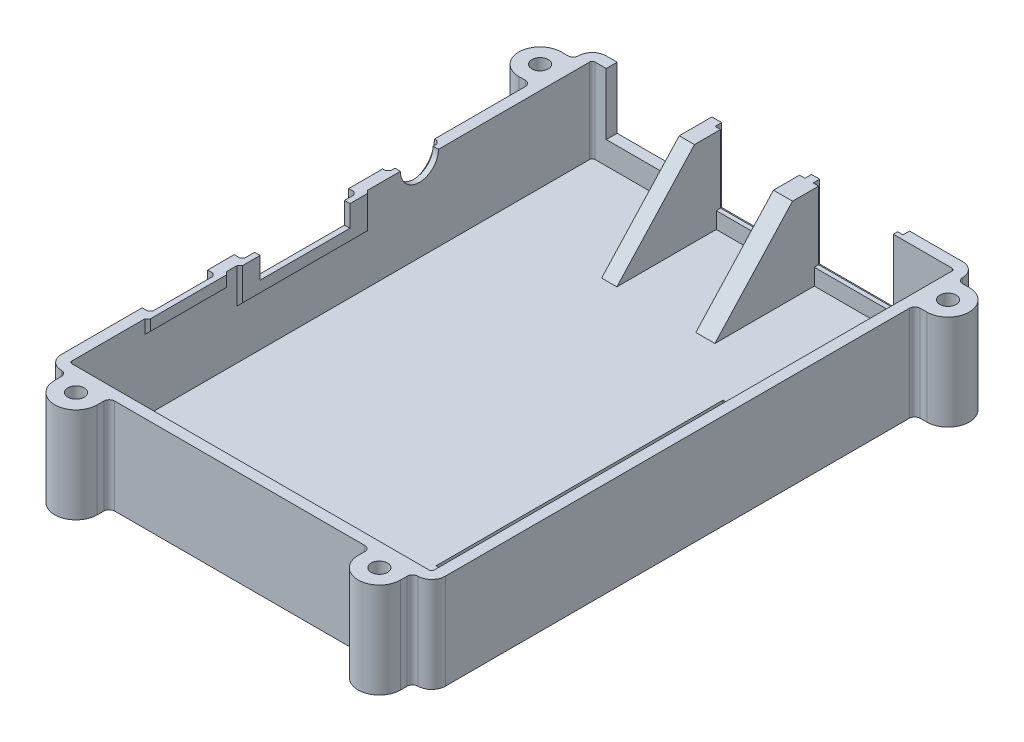
SolidWorks part; units mm, degrees
ref_plane "Front Plane" through (0, 0, 0) normal (0, 0, 1) x (1, 0, 0)
ref_plane "Top Plane" through (0, 0, 0) normal (0, 1, 0) x (1, 0, 0)
ref_plane "Right Plane" through (0, 0, 0) normal (1, 0, 0) x (0, 0, -1)
sketch "Sketch2" plane through (0, 0, 0) normal (0, 1, 0) x (1, 0, 0)
  line L1 (2.5, 0) -> (68, 0)
  line L2 (0, 2.5) -> (0, 97.5)
  line L3 (2.5, 100) -> (68, 100)
  line L4 (70.5, 2.5) -> (70.5, 97.5)
  arc A0 (0, 2.5) -> (2.5, 0) centre (2.5, 2.5) ccw
  arc A1 (68, 0) -> (70.5, 2.5) centre (68, 2.5) ccw
  arc A2 (70.5, 97.5) -> (68, 100) centre (68, 97.5) ccw
  arc A3 (2.5, 100) -> (0, 97.5) centre (2.5, 97.5) ccw
  point P7 (0, 0)
  point P10 (70.5, 0)
  point P13 (70.5, 100)
  point P16 (0, 100)
  dimension "D3" = 2.5
  dimension "D1" = 70.5
  dimension "D2" = 100
extrude "Base" add sketch "Sketch2" along normal blind 17.5
shell "Shell" thickness 2 removed face at (35.25, 17.5, -50)
sketch "Sketch14" plane through (0, 0, 0) normal (0, -1, 0) x (1, 0, 0)
  line L0 (35.25, 0) -> (35.25, -100) construction
  line L2 (68, -100) -> (2.5, -100) construction
  line L3 (-2.2, -88.7) -> (0, -88.7)
  line L4 (0, -97.5) -> (0, -2.5) construction
  line L5 (0, -88.7) -> (0, -96.5)
  line L6 (0, -96.5) -> (-2.2, -96.5)
  line L7 (3.5, 2.2) -> (3.5, 0)
  line L8 (2.5, 0) -> (68, 0) construction
  line L9 (3.5, 0) -> (11.3, 0)
  line L10 (11.3, 0) -> (11.3, 2.2)
  line L11 (72.7, -88.7) -> (70.5, -88.7)
  line L12 (70.5, -96.5) -> (72.7, -96.5)
  line L13 (70.5, -88.7) -> (70.5, -96.5)
  line L14 (59.2, 0) -> (59.2, 2.2)
  line L15 (67, 0) -> (59.2, 0)
  line L16 (67, 2.2) -> (67, 0)
  line L17 (2.5, 0) -> (68, 0) construction
  arc A0 (-2.2, -88.7) -> (-2.2, -96.5) centre (-2.2, -92.6) ccw
  arc A1 (3.5, 2.2) -> (11.3, 2.2) centre (7.4, 2.2) cw
  arc A2 (72.7, -88.7) -> (72.7, -96.5) centre (72.7, -92.6) cw
  arc A3 (67, 2.2) -> (59.2, 2.2) centre (63.1, 2.2) ccw
  dimension "D1" = 2.2
  dimension "D2" = 7.8
  dimension "D3" = 3.5
  dimension "D4" = 3.5
extrude "Clamps" add sketch "Sketch14" against normal up to surface (17.5 mm away) up to face at (35.25, 17.5, -50)
fillet "Clamp Fillets" radius 1 8 edges at (59.2, 8.75, 0) (67, 8.75, 0) (11.3, 8.75, 0) (3.5, 8.75, 0) (0, 8.75, -96.5) (0, 8.75, -88.7) (70.5, 8.75, -88.7) (70.5, 8.75, -96.5)
sketch "Sketch20" plane through (0, 0, 0) normal (0, -1, 0) x (1, 0, 0)
  circle A0 centre (7.4, 2.2) radius 1.5
  circle A1 centre (63.1, 2.2) radius 1.5
  circle A2 centre (72.7, -92.6) radius 1.5
  circle A3 centre (-2.2, -92.6) radius 1.5
  arc A4 (11.3, 2.2) -> (3.5, 2.2) centre (7.4, 2.2) ccw construction
  arc A5 (67, 2.2) -> (59.2, 2.2) centre (63.1, 2.2) ccw construction
  arc A6 (-2.2, -88.7) -> (-2.2, -96.5) centre (-2.2, -92.6) ccw construction
  arc A7 (72.7, -96.5) -> (72.7, -88.7) centre (72.7, -92.6) ccw construction
  dimension "D1" = 3
extrude "Clamp Holes" cut sketch "Sketch20" against normal through all
sketch "Sketch21" plane through (0, 0, 0) normal (0, -1, 0) x (1, 0, 0)
  circle A0 centre (7.4, 2.2) radius 2.5
  circle A1 centre (63.1, 2.2) radius 2.5
  circle A2 centre (72.7, -92.6) radius 2.5
  circle A3 centre (-2.2, -92.6) radius 2.5
  circle A4 centre (-2.2, -92.6) radius 1.5 construction
  circle A5 centre (7.4, 2.2) radius 1.5 construction
  circle A6 centre (63.1, 2.2) radius 1.5 construction
  circle A7 centre (72.7, -92.6) radius 1.5 construction
  dimension "D1" = 5
extrude "Clamp Countersinks" cut sketch "Sketch21" against normal blind 3
chamfer "Clamp Countersink Chamfers" distance 0.3 angle 45 4 edges at (-2.2, 0, -95.1) (72.7, 0, -95.1) (63.1, 0, -0.3) (7.4, 0, -0.3)
sketch "Sketch24" plane through (0, 0, -100) normal (0, 0, -1) x (-1, 0, 0)
  line L0 (-68, 17.5) -> (-2.5, 17.5) construction
  line L1 (-57.25, 17.5) -> (-42.75, 17.5)
  line L2 (-57.25, 17.5) -> (-57.25, 5)
  line L3 (-57.25, 5) -> (-42.75, 5)
  line L4 (-42.75, 17.5) -> (-42.75, 5)
  line L6 (0, 17.5) -> (0, 0) construction
  line L7 (-39.25, 17.5) -> (-24.75, 17.5)
  line L8 (-39.25, 17.5) -> (-39.25, 5)
  line L9 (-39.25, 5) -> (-24.75, 5)
  line L10 (-24.75, 17.5) -> (-24.75, 5)
  dimension "D1" = 14.5
  dimension "D2" = 24.75
  dimension "D3" = 42.75
  dimension "D4" = 12.5
extrude "USB Cutout" cut sketch "Sketch24" against normal blind 18.25
sketch "Sketch25" plane through (0, 0, -100) normal (0, 0, -1) x (-1, 0, 0)
  line L0 (-42.75, 17.5) -> (-39.25, 17.5) construction
  line L1 (-41.75, 17.5) -> (-58.25, 17.5)
  line L2 (-41.75, 17.5) -> (-41.75, 4)
  line L3 (-41.75, 4) -> (-58.25, 4)
  line L4 (-58.25, 17.5) -> (-58.25, 4)
  line L6 (-24.75, 17.5) -> (-2.5, 17.5) construction
  line L7 (-23.75, 17.5) -> (-40.25, 17.5)
  line L8 (-23.75, 17.5) -> (-23.75, 4)
  line L9 (-23.75, 4) -> (-40.25, 4)
  line L10 (-40.25, 17.5) -> (-40.25, 4)
  line L12 (-57.25, 17.5) -> (-57.25, 5) construction
  line L13 (-42.75, 5) -> (-42.75, 17.5) construction
  line L14 (-39.25, 17.5) -> (-39.25, 5) construction
  line L15 (-24.75, 5) -> (-24.75, 17.5) construction
  point P18 (-57.25, 11.25)
  dimension "D1" = 1
  dimension "D2" = 1
  dimension "D3" = 1
  dimension "D4" = 1
  dimension "D5" = 13.5
extrude "USB Approach" cut sketch "Sketch25" against normal blind 1.2
sketch "Sketch26" plane through (42.75, 0, 0) normal (1, 0, 0) x (0, 0, -1)
  line L0 (98, 2) -> (98, 17.5)
  line L1 (98, 17.5) -> (94, 17.5)
  line L2 (98, 2) -> (79.75, 2)
  line L3 (79.75, 2) -> (94, 17.5)
  line L4 (100, 4) -> (100, 17.5) construction
  line L5 (98.8, 5) -> (98.8, 17.5) construction
  dimension "D1" = 6
  dimension "D2" = 19.05
extrude "USB Inner Support" add sketch "Sketch26" against normal up to surface (3.5 mm away) up to face at (39.25, 11.25, -98.4)
sketch "Sketch27" plane through (24.75, 0, 0) normal (1, 0, 0) x (0, 0, -1)
  line L0 (98, 2) -> (98, 17.5)
  line L1 (98, 17.5) -> (94, 17.5)
  line L2 (98, 2) -> (79.75, 2)
  line L3 (79.75, 2) -> (94, 17.5)
  line L4 (100, 4) -> (100, 17.5) construction
  line L5 (98.8, 5) -> (98.8, 17.5) construction
  dimension "D1" = 6
  dimension "D2" = 19.05
extrude "USB Outer Support" add sketch "Sketch27" against normal blind 2.8
sketch "Sketch28" plane through (0, 0, -100) normal (0, 0, -1) x (-1, 0, 0)
  line L0 (-23.75, 17.5) -> (-2.5, 17.5) construction
  line L1 (-21.95, 17.5) -> (-4.55, 17.5)
  line L2 (-21.95, 17.5) -> (-21.95, 6.2)
  line L3 (-21.95, 6.2) -> (-4.55, 6.2)
  line L4 (-4.55, 17.5) -> (-4.55, 6.2)
  line L5 (0, 17.5) -> (0, 0) construction
  dimension "D1" = 17.4
  dimension "D2" = 4.55
  dimension "D3" = 11.3
extrude "RJ45 Cutout" cut sketch "Sketch28" against normal blind 22.7
sketch "Sketch29" plane through (2, 0, 0) normal (1, 0, 0) x (0, 0, -1)
  line L0 (97.5, 17.5) -> (2.5, 17.5) construction
  line L1 (15.85, 17.5) -> (30.85, 17.5)
  line L2 (15.85, 17.5) -> (15.85, 15)
  line L3 (15.85, 15) -> (30.85, 15)
  line L4 (30.85, 17.5) -> (30.85, 15)
  line L5 (0, 17.5) -> (0, 0) construction
  line L6 (32.75, 17.5) -> (56.75, 17.5)
  line L7 (32.75, 17.5) -> (32.75, 11.07)
  line L8 (32.75, 11.07) -> (56.75, 11.07)
  line L9 (56.75, 17.5) -> (56.75, 11.07)
  dimension "D1" = 24
  dimension "D2" = 15
  dimension "D3" = 15.85
  dimension "D4" = 32.75
  dimension "D5" = 2.5
  dimension "D6" = 6.43
extrude "HDMI Support" add sketch "Sketch29" along normal blind 0.5
chamfer "HDMI Support Chamfer" distance 0.5 angle 45 6 edges at (2.5, 14.285, -56.75) (2.5, 11.07, -44.75) (2.5, 14.285, -32.75) (2.5, 16.25, -30.85) (2.5, 15, -23.35) (2.5, 16.25, -15.85)
sketch "Sketch30" plane through (0, 0, 0) normal (-1, 0, 0) x (0, 0, 1)
  line L0 (-87.7, 17.5) -> (-2.5, 17.5) construction
  line L1 (-34.25, 17.5) -> (-55.25, 17.5)
  line L2 (-34.25, 17.5) -> (-34.25, 11.57)
  line L3 (-34.25, 11.57) -> (-55.25, 11.57)
  line L4 (-55.25, 17.5) -> (-55.25, 11.57)
  line L5 (0, 17.5) -> (0, 0) construction
  line L6 (-29.35, 17.5) -> (-17.35, 17.5)
  line L7 (-29.35, 17.5) -> (-29.35, 15.5)
  line L8 (-29.35, 15.5) -> (-17.35, 15.5)
  line L9 (-17.35, 17.5) -> (-17.35, 15.5)
  dimension "D1" = 12
  dimension "D2" = 21
  dimension "D3" = 17.35
  dimension "D4" = 34.25
  dimension "D5" = 5.93
  dimension "D6" = 2
extrude "HDMI Approach" cut sketch "Sketch30" against normal blind 1.5
sketch "Sketch31" plane through (1.5, 0, 0) normal (-1, 0, 0) x (0, 0, 1)
  line L0 (-34.25, 17.5) -> (-55.25, 17.5) construction
  line L1 (-53, 17.5) -> (-36.5, 17.5)
  line L2 (-53, 17.5) -> (-53, 13.57)
  line L3 (-53, 13.57) -> (-36.5, 13.57)
  line L4 (-36.5, 17.5) -> (-36.5, 13.57)
  line L5 (-55.25, 17.5) -> (-55.25, 11.57) construction
  line L6 (-34.25, 11.57) -> (-34.25, 17.5) construction
  line L7 (-55.25, 11.57) -> (-34.25, 11.57) construction
  dimension "D1" = 2.25
  dimension "D2" = 2.25
  dimension "D3" = 2
extrude "HDMI Cutout" cut sketch "Sketch31" against normal blind 1
chamfer "HDMI Approach Chamfer" distance 0.5 angle 45 6 edges at (1.5, 16.5, -17.35) (1.5, 15.5, -23.35) (1.5, 16.5, -29.35) (1.5, 14.535, -34.25) (1.5, 11.57, -44.75) (1.5, 14.535, -55.25)
sketch "Sketch32" plane through (0, 0, 0) normal (-1, 0, 0) x (0, 0, 1)
  line L0 (-87.7, 17.5) -> (-55.25, 17.5) construction
  line L1 (0, 17.5) -> (0, 0) construction
  circle A0 centre (-66.25, 17.5) radius 3.5
  dimension "D1" = 7
  dimension "D2" = 66.25
extrude "Audio Cutout" cut sketch "Sketch32" against normal blind 2
sketch "Sketch33" plane through (0, 0, 0) normal (-1, 0, 0) x (0, 0, 1)
  circle A0 centre (-66.25, 17.5) radius 4.75
  arc A1 (-69.75, 17.5) -> (-62.75, 17.5) centre (-66.25, 17.5) ccw construction
  dimension "D1" = 9.5
extrude "Audio Approach" cut sketch "Sketch33" against normal blind 1
chamfer "Audio Approach Chamfer" distance 0.5 angle 45 1 edges at (1, 12.75, -66.25)
sketch "Sketch34" plane through (0, 0, 0) normal (0, -1, 0) x (1, 0, 0)
  line L0 (70.5, -2.5) -> (70.5, -87.7) construction
  line L1 (52.5, -18.8) -> (58.5, -18.8)
  line L2 (52.5, -18.8) -> (52.5, -71.5)
  line L3 (52.5, -71.5) -> (58.5, -71.5)
  line L4 (58.5, -18.8) -> (58.5, -71.5)
  line L5 (12.3, 0) -> (58.2, 0) construction
  point P6 (55.5, -18.8)
  dimension "D1" = 6
  dimension "D2" = 52.7
  dimension "D3" = 12
  dimension "D4" = 18.8
extrude "Header Cutout" cut sketch "Sketch34" against normal blind 2
sketch "Sketch35" plane through (0, 0, 0) normal (0, -1, 0) x (1, 0, 0)
  line L0 (55.5, -18.8) -> (55.5, -71.5) construction
  line L1 (58.5, -18.8) -> (52.5, -18.8) construction
  line L2 (52.5, -71.5) -> (58.5, -71.5) construction
  line L3 (52.5, -45.15) -> (58.5, -45.15) construction
  line L4 (52.5, -18.8) -> (52.5, -71.5) construction
  line L5 (58.5, -71.5) -> (58.5, -18.8) construction
  line L6 (56, -18.8) -> (55, -18.8)
  line L7 (55, -18.8) -> (55, -19.8)
  line L8 (55, -19.8) -> (53.5, -19.8)
  line L9 (53.5, -19.8) -> (53.5, -24.7625)
  line L10 (53.5, -24.7625) -> (52.5, -24.7625)
  line L11 (52.5, -24.7625) -> (52.5, -25.7625)
  line L12 (52.5, -25.7625) -> (53.5, -25.7625)
  line L13 (53.5, -25.7625) -> (53.5, -37.6875)
  line L14 (53.5, -37.6875) -> (52.5, -37.6875)
  line L15 (52.5, -37.6875) -> (52.5, -38.6875)
  line L16 (52.5, -38.6875) -> (53.5, -38.6875)
  line L17 (53.5, -38.6875) -> (53.5, -43.65)
  line L18 (53.5, -43.65) -> (55, -43.65)
  line L19 (55, -43.65) -> (55, -44.65)
  line L20 (55, -44.65) -> (52.5, -44.65)
  line L21 (52.5, -44.65) -> (52.5, -45.65)
  line L22 (56, -71.5) -> (55, -71.5)
  line L23 (55, -45.65) -> (52.5, -45.65)
  line L24 (55, -46.65) -> (55, -45.65)
  line L25 (53.5, -46.65) -> (55, -46.65)
  line L26 (53.5, -51.6125) -> (53.5, -46.65)
  line L27 (52.5, -51.6125) -> (53.5, -51.6125)
  line L28 (52.5, -52.6125) -> (52.5, -51.6125)
  line L29 (53.5, -52.6125) -> (52.5, -52.6125)
  line L30 (53.5, -64.5375) -> (53.5, -52.6125)
  line L31 (52.5, -64.5375) -> (53.5, -64.5375)
  line L32 (52.5, -65.5375) -> (52.5, -64.5375)
  line L33 (53.5, -65.5375) -> (52.5, -65.5375)
  line L34 (53.5, -70.5) -> (53.5, -65.5375)
  line L35 (55, -70.5) -> (53.5, -70.5)
  line L36 (55, -71.5) -> (55, -70.5)
  line L37 (56, -71.5) -> (56, -70.5)
  line L38 (56, -70.5) -> (57.5, -70.5)
  line L39 (57.5, -70.5) -> (57.5, -65.5375)
  line L40 (57.5, -65.5375) -> (58.5, -65.5375)
  line L41 (58.5, -65.5375) -> (58.5, -64.5375)
  line L42 (58.5, -64.5375) -> (57.5, -64.5375)
  line L43 (57.5, -64.5375) -> (57.5, -52.6125)
  line L44 (57.5, -52.6125) -> (58.5, -52.6125)
  line L45 (58.5, -52.6125) -> (58.5, -51.6125)
  line L46 (58.5, -51.6125) -> (57.5, -51.6125)
  line L47 (57.5, -51.6125) -> (57.5, -46.65)
  line L48 (57.5, -46.65) -> (56, -46.65)
  line L49 (56, -46.65) -> (56, -45.65)
  line L50 (56, -45.65) -> (58.5, -45.65)
  line L51 (58.5, -44.65) -> (58.5, -45.65)
  line L52 (56, -44.65) -> (58.5, -44.65)
  line L53 (56, -43.65) -> (56, -44.65)
  line L54 (57.5, -43.65) -> (56, -43.65)
  line L55 (57.5, -38.6875) -> (57.5, -43.65)
  line L56 (58.5, -38.6875) -> (57.5, -38.6875)
  line L57 (58.5, -37.6875) -> (58.5, -38.6875)
  line L58 (57.5, -37.6875) -> (58.5, -37.6875)
  line L59 (57.5, -25.7625) -> (57.5, -37.6875)
  line L60 (58.5, -25.7625) -> (57.5, -25.7625)
  line L61 (58.5, -24.7625) -> (58.5, -25.7625)
  line L62 (57.5, -24.7625) -> (58.5, -24.7625)
  line L63 (57.5, -19.8) -> (57.5, -24.7625)
  line L64 (56, -19.8) -> (57.5, -19.8)
  line L65 (56, -18.8) -> (56, -19.8)
  dimension "D1" = 0.5
  dimension "D2" = 1
  dimension "D3" = 1.5
  dimension "D4" = 11.925
extrude "Header Cover" add sketch "Sketch35" against normal blind 1
